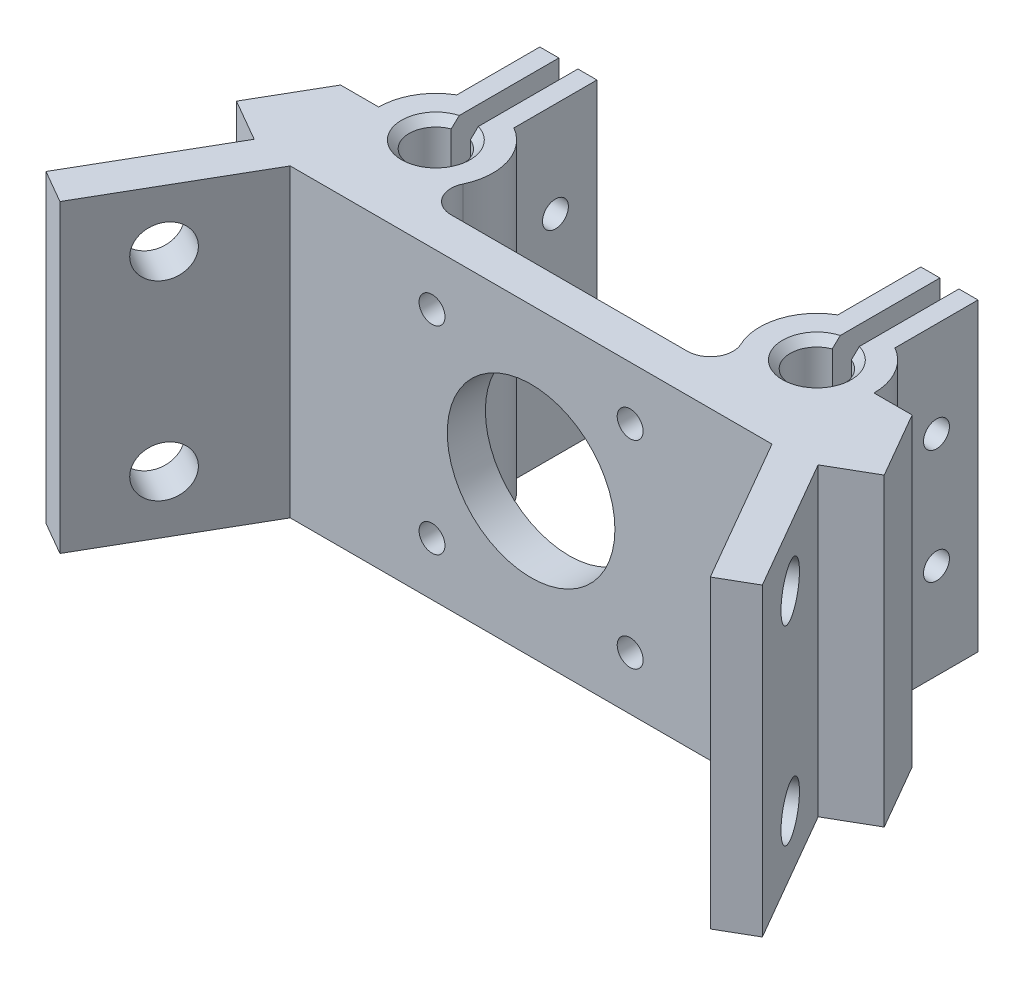
SolidWorks part; units mm, degrees
ref_plane "Front Plane" through (0, 0, 0) normal (0, 0, 1) x (1, 0, 0)
ref_plane "Top Plane" through (0, 0, 0) normal (0, 1, 0) x (1, 0, 0)
ref_plane "Right Plane" through (0, 0, 0) normal (1, 0, 0) x (0, 0, -1)
sketch "Sketch1" plane through (0, 0, 0) normal (0, 1, 0) x (1, 0, 0)
  line L0 (0, 116.7614) -> (0, -100.8523) construction
  line L1 (23.75, 110.7692) -> (23.75, 124.8951)
  line L2 (28.75, 124.8951) -> (28.75, 113.9952)
  line L3 (25, -2.1466) -> (25, 14.9187) construction
  line L4 (23.75, 124.8951) -> (21.25, 124.8951)
  line L5 (21.25, 124.8951) -> (21.25, 113.9952)
  line L6 (26.25, 124.8951) -> (28.75, 124.8951)
  line L7 (26.25, 110.7692) -> (26.25, 124.8951)
  line L8 (-25, -2.3511) -> (-25, 14.7142) construction
  line L9 (-26.25, 110.7692) -> (-26.25, 124.8951)
  line L10 (-26.25, 124.8951) -> (-28.75, 124.8951)
  line L11 (-21.25, 124.8951) -> (-21.25, 113.9952)
  line L12 (-23.75, 124.8951) -> (-21.25, 124.8951)
  line L13 (-28.75, 124.8951) -> (-28.75, 113.9952)
  line L14 (-23.75, 110.7692) -> (-23.75, 124.8951)
  line L15 (-15.5132, 100) -> (15.5132, 100)
  line L16 (-31.611, 95) -> (31.611, 95)
  line L17 (-32.5, 107.5) -> (-37.5, 107.5)
  line L18 (0, 100) -> (-86.6025, -50) construction
  line L19 (-86.6025, -50) -> (86.6025, -50) construction
  line L20 (86.6025, -50) -> (0, 100) construction
  line L21 (-37.5, 107.5) -> (-42.5, 98.8397)
  line L22 (-47.0007, 78.3442) -> (-42.6706, 75.8442)
  line L23 (-42.6706, 75.8442) -> (-31.611, 95)
  line L24 (42.6706, 75.8442) -> (31.611, 95)
  line L25 (47.0007, 78.3442) -> (42.6706, 75.8442)
  line L26 (47.0007, 78.3442) -> (37.0007, 95.6647)
  line L27 (32.5, 107.5) -> (37.5, 107.5)
  line L28 (-47.0007, 78.3442) -> (-37.0007, 95.6647)
  line L29 (-37.0007, 95.6647) -> (-42.5, 98.8397)
  line L30 (37.0007, 95.6647) -> (42.5, 98.8397)
  line L31 (37.5, 107.5) -> (42.5, 98.8397)
  arc A0 (21.25, 113.9952) -> (18.2237, 104.2857) centre (25, 107.5) ccw
  arc A1 (23.75, 110.7692) -> (26.25, 110.7692) centre (25, 107.5) ccw
  arc A2 (-23.75, 110.7692) -> (-26.25, 110.7692) centre (-25, 107.5) cw
  arc A3 (-21.25, 113.9952) -> (-18.2237, 104.2857) centre (-25, 107.5) cw
  circle A4 centre (0, 0) radius 100 construction
  circle A5 centre (0, 0) radius 50 construction
  arc A6 (15.5132, 100) -> (18.2237, 104.2857) centre (15.5132, 103) ccw
  arc A7 (-18.2237, 104.2857) -> (-15.5132, 100) centre (-15.5132, 103) ccw
  arc A8 (-28.75, 113.9952) -> (-32.5, 107.5) centre (-25, 107.5) ccw
  arc A9 (28.75, 113.9952) -> (32.5, 107.5) centre (25, 107.5) cw
  point P12 (23.75, 114.8951)
  point P13 (26.25, 114.8951)
  point P27 (-26.25, 114.8951)
  point P28 (-23.75, 114.8951)
  dimension "D2" = 7
  dimension "D3" = 4
  dimension "D5" = 2.5
  dimension "D10" = 120
  dimension "D11" = 10
  dimension "D7" = 200
  dimension "D13" = 3
  dimension "D14" = 7.5
  dimension "D1" = 50
  dimension "D4" = 10
  dimension "D6" = 2.5
  dimension "D8" = 5
  dimension "D9" = 5
  dimension "D12" = 5
  dimension "D15" = 20
  dimension "D16" = 6.35
extrude "Boss-Extrude1" add sketch "Sketch1" along normal blind 40 contours A3 L11 L12 L14 A2 L9 L10 L13 | A1 L1 L4 L5 A0 L2 L6 L7 | L15 A3 L16 A0 region at (25, 0, -102.9397)
sketch "Sketch2" plane through (0, 0, 0) normal (1, 0, 0) x (0, 0, -1)
  line L0 (119.4451, 40) -> (119.4451, 0) construction
  line L3 (124.8951, 20) -> (113.9952, 20) construction
  line L4 (124.8951, 40) -> (124.8951, 0) construction
  line L6 (124.8951, 40) -> (113.9952, 40) construction
  line L7 (124.8951, 0) -> (113.9952, 0) construction
  circle A0 centre (119.4451, 27.5) radius 1.7
  circle A1 centre (119.4451, 12.5) radius 1.7
  dimension "D1" = 3.4
  dimension "D2" = 15
extrude "Cut-Extrude1" cut sketch "Sketch2" against normal mid plane 57.5
sketch "Sketch4" plane through (0, 0, -95) normal (0, 0, 1) x (1, 0, 0)
  line L1 (-13, 7) -> (13, 7) construction
  line L2 (-13, 7) -> (-13, 33) construction
  line L3 (-13, 33) -> (13, 33) construction
  line L4 (13, 7) -> (13, 33) construction
  line L5 (-13, 7) -> (13, 33) construction
  line L6 (-13, 33) -> (13, 7) construction
  line L7 (17.75, 2.25) -> (-17.75, 2.25)
  line L8 (17.75, 2.25) -> (17.75, 37.75)
  line L9 (17.75, 37.75) -> (-17.75, 37.75)
  line L10 (-17.75, 2.25) -> (-17.75, 37.75)
  line L11 (17.75, 2.25) -> (-17.75, 37.75) construction
  line L12 (17.75, 37.75) -> (-17.75, 2.25) construction
  circle A0 centre (-13, 33) radius 1.7
  circle A1 centre (13, 33) radius 1.7
  circle A2 centre (13, 7) radius 1.7
  circle A3 centre (-13, 7) radius 1.7
  circle A4 centre (0, 20) radius 11
  circle A5 centre (-13, 33) radius 2.9337 construction
  point P0 (0, 20)
  point P16 (0, 20)
  dimension "D2" = 3.4
  dimension "D5" = 22
  dimension "D7" = 5.8674
  dimension "D1" = 26
  dimension "D4" = 20
  dimension "D6" = 35.5
  dimension "D3" = 4
extrude "Cut-Extrude2" cut sketch "Sketch4" against normal blind 20 contours A0 | A4 | A1 | A2 | A3 region at (-13, 33, -95) region at (13, 33, -95) region at (13, 7, -95) region at (-13, 7, -95) region at (0, 20, -95)
chamfer "Chamfer1" distance 1 angle 45 2 edges at (25, 40, -104) (-25, 40, -104)
sketch "Sketch5" plane through (-69.1746, 0, -39.938) normal (-0.866, 0, -0.5) x (-0.5, 0, 0.866)
  line L0 (-44.3477, 20) -> (-64.3477, 20) construction
  line L1 (-44.3477, 40) -> (-44.3477, 0) construction
  line L2 (-64.3477, 40) -> (-64.3477, 0) construction
  line L3 (-54.3477, 20) -> (-54.3477, 32.5) construction
  line L4 (-54.3477, 20) -> (-54.3477, 7.5) construction
  circle A0 centre (-54.3477, 32.5) radius 3.3
  circle A1 centre (-54.3477, 7.5) radius 3.3
  dimension "D2" = 6.6
  dimension "D3" = 25
extrude "Cut-Extrude3" cut sketch "Sketch5" against normal up to next
mirror "Mirror1" about plane through (0, 0, 0) normal (1, 0, 0) of "Cut-Extrude3"
equation "\"RodSpacing\"= 50"
equation "\"D1@Sketch1\"=\"RodSpacing\""
equation "\"Clamp_Gap\"=2.5"
equation "\"D5@Sketch1\"=\"Clamp_Gap\""
equation "\"D6@Sketch1\"=\"Clamp_Gap\""
equation "\"D1@Cut-Extrude1\"=\"RodSpacing\"+(3*\"Clamp_Gap\")"
